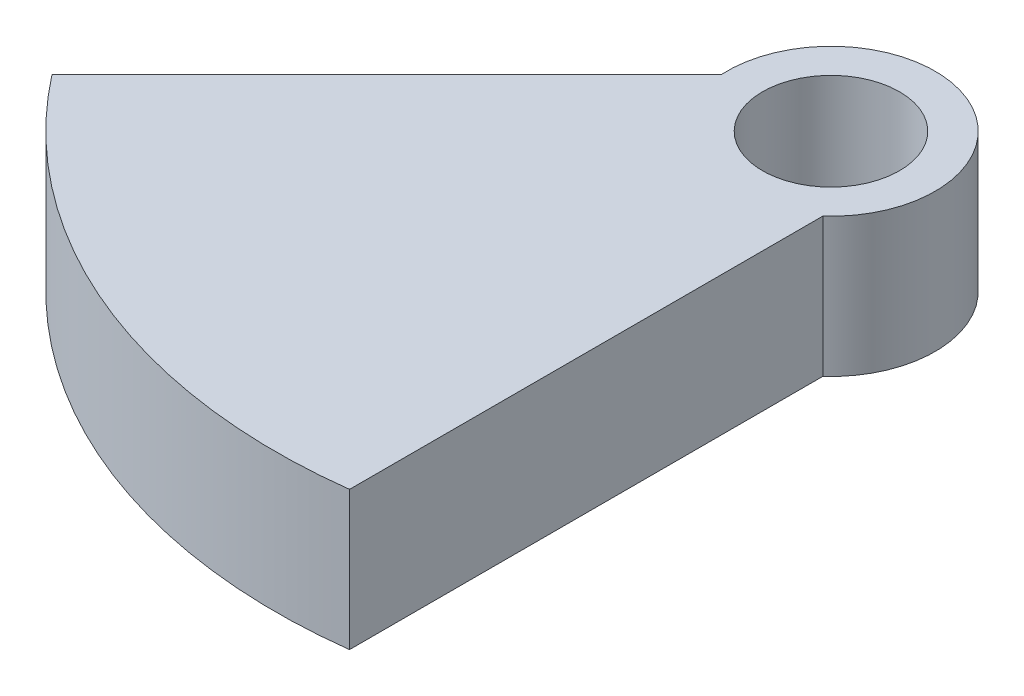
SolidWorks part; units mm, degrees
ref_plane "Front Plane" through (0, 0, 0) normal (0, 0, 1) x (1, 0, 0)
ref_plane "Top Plane" through (0, 0, 0) normal (0, 1, 0) x (1, 0, 0)
ref_plane "Right Plane" through (0, 0, 0) normal (1, 0, 0) x (0, 0, -1)
sketch "Sketch1" plane through (0, 0, 0) normal (0, 1, 0) x (1, 0, 0)
  line L0 (0, 0) -> (-53.8815, -53.8815) construction
  line L1 (0, 0) -> (0, -76.2) construction
  line L2 (-14.2654, -0.795) -> (-60.1941, -46.7237)
  line L3 (9.525, -10.6493) -> (9.525, -75.6023)
  circle A0 centre (0, 0) radius 9.398
  circle A1 centre (0, 0) radius 14.2875
  circle A2 centre (0, 0) radius 76.2 construction
  arc A3 (-60.1941, -46.7237) -> (9.525, -75.6023) centre (0, 0) ccw
  dimension "D1" = 18.796
  dimension "D2" = 28.575
  dimension "D3" = 45
  dimension "D4" = 76.2
  dimension "D5" = 9.525
  dimension "D6" = 9.525
extrude "Boss-Extrude2" add sketch "Sketch1" along normal blind 19.05 contours L2 A3 L3 A1 | A1 A0 region at (-17.9361, 0, 43.3015) region at (-0.3864, 0, -13.878)
